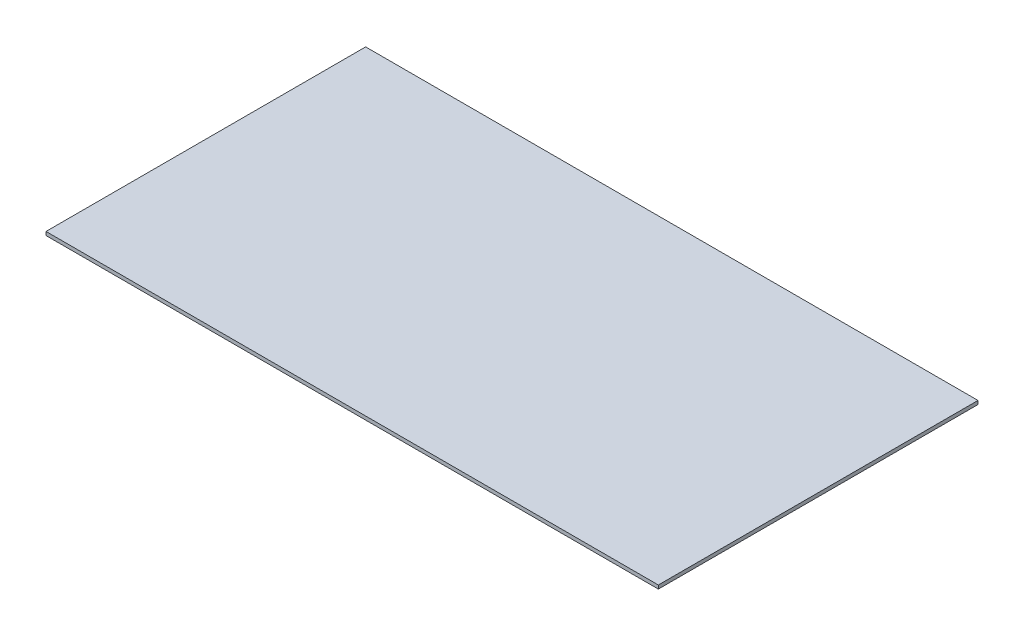
SolidWorks part; units mm, degrees
material "5052-H34"
ref_plane "Front Plane" through (0, 0, 0) normal (0, 0, 1) x (1, 0, 0)
ref_plane "Top Plane" through (0, 0, 0) normal (0, 1, 0) x (1, 0, 0)
ref_plane "Right Plane" through (0, 0, 0) normal (1, 0, 0) x (0, 0, -1)
sketch "Sketch1" plane through (0, 0, 0) normal (0, 0, 1) x (1, 0, 0)
  line L0 (-580.595, 2.8542) -> (-36.865, 2.8542)
  line L1 (-36.865, 2.8542) -> (-36.865, -0.3208)
  line L3 (-36.865, -0.3208) -> (-580.595, -0.3208)
  line L6 (-580.595, 2.8542) -> (-580.595, -0.3208)
  point P2 (-580.595, 2.8542)
  dimension "D1" = 3.175
  dimension "D2" = 543.73
  dimension "D3" = 36.865
  dimension "D4" = 2.8542
extrude "Boss-Extrude1" add sketch "Sketch1" along normal blind 283.825
sketch "GasketGroove" plane through (0, -0.3208, 0) normal (0, -1, 0) x (1, 0, 0)
  line L0 (-577.595, 279.825) -> (-577.595, 4)
  line L1 (-576.595, 3) -> (-40.865, 3)
  line L2 (-39.865, 4) -> (-39.865, 279.825)
  line L3 (-40.865, 280.825) -> (-576.595, 280.825)
  line L4 (-579.595, 282.825) -> (-579.595, 1) construction
  line L5 (-577.595, 282.825) -> (-577.595, 1) construction
  line L6 (-37.865, 280.825) -> (-579.595, 280.825) construction
  line L7 (-579.595, 3) -> (-37.865, 3) construction
  line L8 (-39.865, 1) -> (-39.865, 282.825) construction
  line L9 (-579.595, 1) -> (-37.865, 1) construction
  line L10 (-37.865, 282.825) -> (-579.595, 282.825) construction
  line L11 (-37.865, 1) -> (-37.865, 282.825) construction
  line L14 (-37.865, 1) -> (-37.865, 282.825)
  line L15 (-579.595, 1) -> (-37.865, 1)
  line L16 (-579.595, 282.825) -> (-579.595, 1)
  line L17 (-37.865, 282.825) -> (-579.595, 282.825)
  line L18 (-37.865, 2) -> (-37.865, 281.825)
  line L19 (-578.595, 1) -> (-38.865, 1)
  line L20 (-579.595, 281.825) -> (-579.595, 2)
  line L21 (-38.865, 282.825) -> (-578.595, 282.825)
  arc A0 (-579.595, 2) -> (-578.595, 1) centre (-578.595, 2) ccw
  arc A1 (-579.595, 281.825) -> (-578.595, 282.825) centre (-578.595, 281.825) cw
  arc A2 (-37.865, 281.825) -> (-38.865, 282.825) centre (-38.865, 281.825) ccw
  arc A3 (-38.865, 1) -> (-37.865, 2) centre (-38.865, 2) ccw
  arc A4 (-40.865, 3) -> (-39.865, 4) centre (-40.865, 4) ccw
  arc A5 (-576.595, 3) -> (-577.595, 4) centre (-576.595, 4) cw
  arc A6 (-576.595, 280.825) -> (-577.595, 279.825) centre (-576.595, 279.825) ccw
  arc A7 (-39.865, 279.825) -> (-40.865, 280.825) centre (-40.865, 279.825) ccw
  dimension "D6" = 1
  dimension "D7" = 1
  dimension "D8" = 1
  dimension "D9" = 1
  dimension "D10" = 1
  dimension "D11" = 1
  dimension "D12" = 1
  dimension "D13" = 1
  dimension "D1" = 1
  dimension "D2" = 2
  dimension "D3" = 2
  dimension "D4" = 2
  dimension "D5" = 2
extrude "Cut-Extrude1" cut sketch "GasketGroove" against normal blind 1.3
sketch "Sketch2" plane through (0, 2.8542, 0) normal (0, 1, 0) x (1, 0, 0)
  line L0 (-36.865, -283.825) -> (-580.595, -283.825) construction
  line L4 (-580.595, -283.825) -> (-580.595, 0) construction
  line L5 (-480.595, -283.825) -> (-471.595, -283.825)
  line L6 (-480.595, -283.825) -> (-480.595, -292.825)
  line L7 (-480.595, -292.825) -> (-471.595, -292.825)
  line L8 (-471.595, -283.825) -> (-471.595, -292.825)
  line L9 (-145.865, -283.825) -> (-136.865, -283.825)
  line L10 (-145.865, -283.825) -> (-145.865, -292.825)
  line L11 (-145.865, -292.825) -> (-136.865, -292.825)
  line L12 (-136.865, -283.825) -> (-136.865, -292.825)
  line L17 (-136.865, 0) -> (-145.865, 0)
  line L18 (-136.865, 0) -> (-136.865, 9)
  line L19 (-136.865, 9) -> (-145.865, 9)
  line L20 (-145.865, 0) -> (-145.865, 9)
  line L21 (-36.865, -283.825) -> (-36.865, 0) construction
  line L22 (-480.595, -288.325) -> (-471.595, -288.325) construction
  line L23 (-480.595, 0) -> (-471.595, 0)
  line L24 (-480.595, 0) -> (-480.595, 9)
  line L25 (-480.595, 9) -> (-471.595, 9)
  line L26 (-471.595, 0) -> (-471.595, 9)
  line L27 (-141.365, -292.825) -> (-141.365, -283.825) construction
  line L28 (-145.865, 4.5) -> (-136.865, 4.5) construction
  line L29 (-480.595, 4.5) -> (-471.595, 4.5) construction
  circle A0 centre (-476.095, -288.325) radius 1.925
  circle A1 centre (-141.365, -288.325) radius 1.925
  circle A2 centre (-141.365, 4.5) radius 1.925
  circle A3 centre (-476.095, 4.5) radius 1.925
  dimension "D10" = 3.85
  dimension "D11" = 9
  dimension "D1" = 9
  dimension "D2" = 9
  dimension "D3" = 9
  dimension "D4" = 100
  dimension "D5" = 100
  dimension "D6" = 100
  dimension "D7" = 9
  dimension "D8" = 100
  dimension "D9" = 9
  dimension "D14" = 4.5
extrude "Boss-Extrude2" add sketch "Sketch2" against normal blind 3.125
sketch "Sketch3" plane through (0, 2.8542, 0) normal (0, 1, 0) x (1, 0, 0)
  line L1 (-471.595, 0) -> (-480.595, 0)
  line L2 (-471.595, 0) -> (-471.595, 9)
  line L3 (-471.595, 9) -> (-480.595, 9)
  line L4 (-480.595, 0) -> (-480.595, 9)
  line L5 (-136.865, 0) -> (-145.865, 0)
  line L6 (-136.865, 0) -> (-136.865, 9)
  line L7 (-136.865, 9) -> (-145.865, 9)
  line L8 (-145.865, 0) -> (-145.865, 9)
  line L9 (-145.865, -283.825) -> (-136.865, -283.825)
  line L10 (-145.865, -283.825) -> (-145.865, -292.825)
  line L11 (-145.865, -292.825) -> (-136.865, -292.825)
  line L12 (-136.865, -283.825) -> (-136.865, -292.825)
  line L13 (-480.595, -283.825) -> (-471.595, -283.825)
  line L14 (-480.595, -283.825) -> (-480.595, -292.825)
  line L15 (-480.595, -292.825) -> (-471.595, -292.825)
  line L16 (-471.595, -283.825) -> (-471.595, -292.825)
extrude "Cut-Extrude2" cut sketch "Sketch3" against normal blind 10
